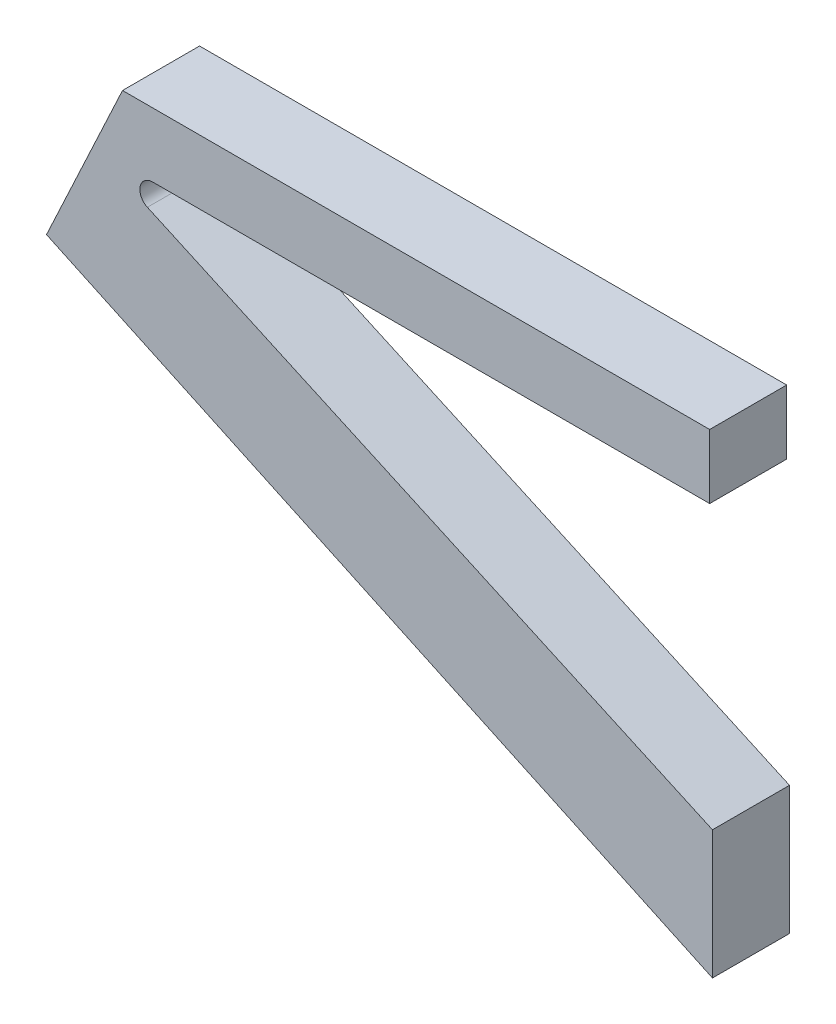
SolidWorks part; units mm, degrees
ref_plane "Front Plane" through (0, 0, 0) normal (0, 0, 1) x (1, 0, 0)
ref_plane "Top Plane" through (0, 0, 0) normal (0, 1, 0) x (1, 0, 0)
ref_plane "Right Plane" through (0, 0, 0) normal (1, 0, 0) x (0, 0, -1)
sketch "Sketch2" plane through (0, 0, 0) normal (0, 0, 1) x (1, 0, 0)
  line L0 (0, 0) -> (0, -5)
  line L1 (0, -5) -> (-48.01, -5)
  line L2 (0, 0) -> (-45.74, 0)
  line L3 (-45.74, 0) -> (-51.6611, -12.6862)
  line L4 (-51.6611, -12.6862) -> (0.2175, -36.8973)
  line L5 (0.2175, -36.8973) -> (0.2175, -26.8973)
  line L6 (-48.01, -5) -> (0.2175, -26.8973)
  dimension "D1" = 5
  dimension "D2" = 48.01
  dimension "D3" = 45.74
  dimension "D4" = 14
  dimension "D5" = 244.98
  dimension "D6" = 57.25
  dimension "D7" = 10
  dimension "D8" = 24.42
  dimension "D9" = 52.9659
extrude "Boss-Extrude1" add sketch "Sketch2" along normal blind 3 and the other way blind 3 contours L2 L3 L4 L5 L6 L1 L0
fillet "Fillet1" radius 1 1 edges at (-48.01, -5, 0)
